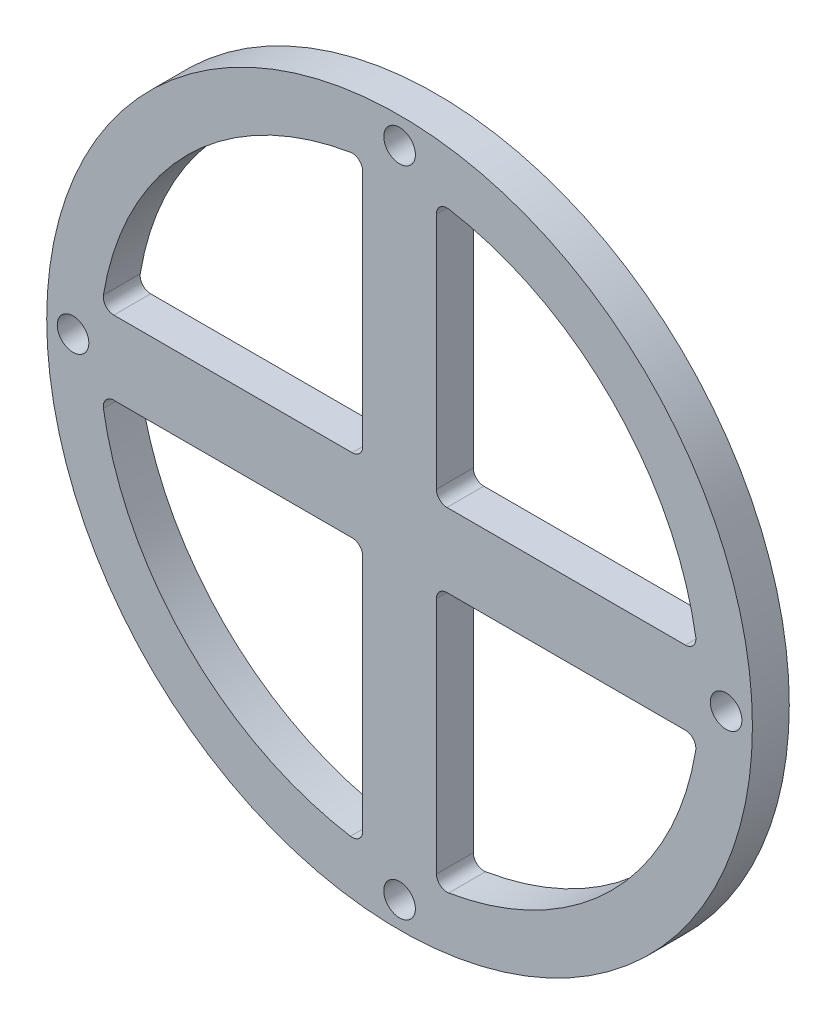
SolidWorks part; units mm, degrees
ref_plane "Piano frontale" through (0, 0, 0) normal (0, 0, 1) x (1, 0, 0)
ref_plane "Piano superiore" through (0, 0, 0) normal (0, 1, 0) x (1, 0, 0)
ref_plane "Piano destro" through (0, 0, 0) normal (1, 0, 0) x (0, 0, -1)
sketch "Schizzo2" plane through (0, 0, 0) normal (0, 0, 1) x (1, 0, 0)
  line L0 (7, 9) -> (7, 54.2586)
  line L1 (-9, 7) -> (-54.2586, 7)
  line L2 (-9, -7) -> (-54.2586, -7)
  line L4 (7, -54.2586) -> (7, -9)
  line L5 (-7, 54.2586) -> (-7, 9)
  line L6 (54.2586, -7) -> (9, -7)
  line L7 (54.2586, 7) -> (9, 7)
  line L8 (-7, -9) -> (-7, -54.2586)
  circle A0 centre (0, 0) radius 67
  arc A1 (9.3273, -56.2317) -> (56.2317, -9.3273) centre (0, 0) ccw
  arc A2 (56.2317, 9.3273) -> (9.3273, 56.2317) centre (0, 0) ccw
  arc A3 (-9.3273, 56.2317) -> (-56.2317, 9.3273) centre (0, 0) ccw
  arc A4 (-56.2317, -9.3273) -> (-9.3273, -56.2317) centre (0, 0) ccw
  arc A5 (-9.3273, -56.2317) -> (-7, -54.2586) centre (-9, -54.2586) ccw
  arc A6 (-7, -9) -> (-9, -7) centre (-9, -9) ccw
  arc A7 (-56.2317, -9.3273) -> (-54.2586, -7) centre (-54.2586, -9) cw
  arc A8 (54.2586, -7) -> (56.2317, -9.3273) centre (54.2586, -9) cw
  arc A9 (7, -9) -> (9, -7) centre (9, -9) cw
  arc A10 (7, -54.2586) -> (9.3273, -56.2317) centre (9, -54.2586) ccw
  arc A11 (54.2586, 7) -> (56.2317, 9.3273) centre (54.2586, 9) ccw
  arc A12 (9.3273, 56.2317) -> (7, 54.2586) centre (9, 54.2586) ccw
  arc A13 (7, 9) -> (9, 7) centre (9, 9) ccw
  arc A14 (-7, 9) -> (-9, 7) centre (-9, 9) cw
  arc A15 (-56.2317, 9.3273) -> (-54.2586, 7) centre (-54.2586, 9) ccw
  arc A16 (-7, 54.2586) -> (-9.3273, 56.2317) centre (-9, 54.2586) ccw
  point P20 (-7, -7)
  point P23 (-56.5685, -7)
  point P32 (56.5685, 7)
  point P35 (7, 56.5685)
  point P40 (-7, 7)
  point P43 (-56.5685, 7)
  point P46 (-7, 56.5685)
  dimension "D1" = 2
extrude "Estrusione-Estrusione1" add sketch "Schizzo2" along normal blind 7 contours A0 A4 L2 L8 A3 L5 L1 A2 L7 L0 A1 L4 L6 region at (0, 0, 0)
sketch "Schizzo3" plane through (0, 0, 0) normal (0, 0, 1) x (1, 0, 0)
  line L0 (0, 0) -> (0, 62)
  circle A0 centre (0, 62) radius 3
  dimension "D1" = 6
extrude "Taglio-Estrusione2" cut sketch "Schizzo3" along normal up to surface (7 mm away) contours A0 up to face at (-25.0018, 25.0018, 7)
ref_axis "Assi1" through (0, 0, 52.6425) along (0, 0, -1)
pattern_circular "RipetizioneCircolare1" count 4 every 90 about axis through (0, 0, 52.6425) along (0, 0, -1) of "Taglio-Estrusione2"
